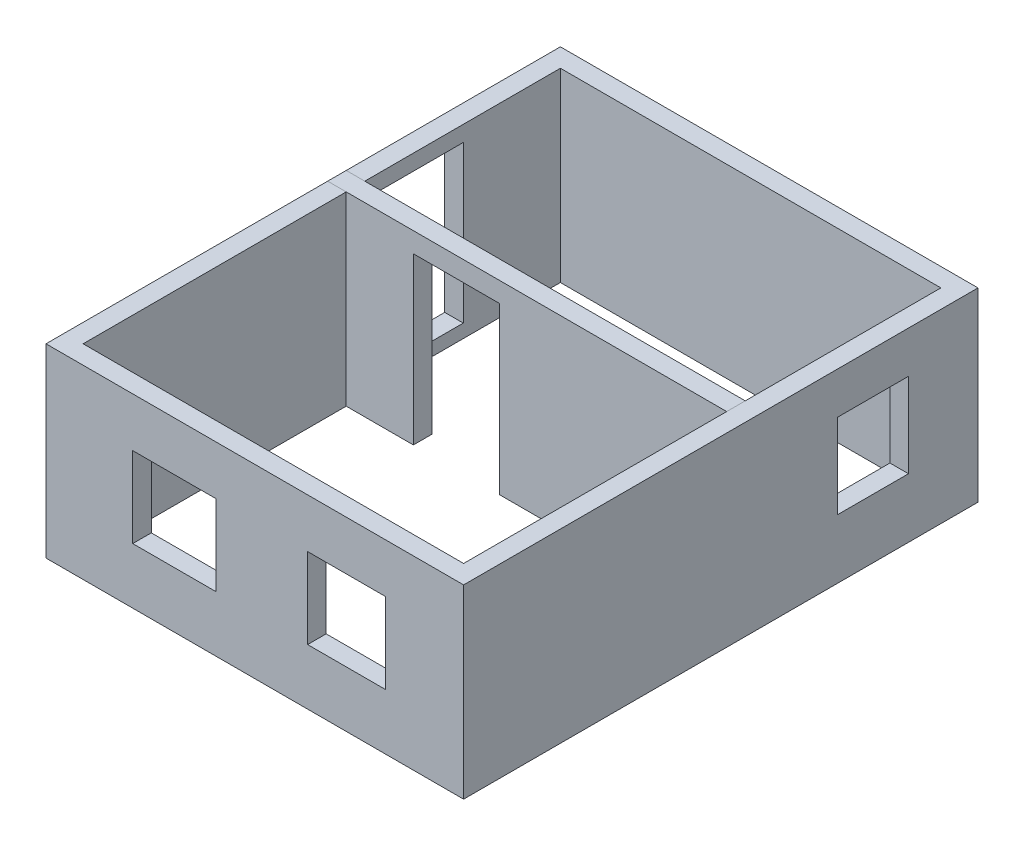
SolidWorks part; units mm, degrees
ref_plane "Спереди" through (0, 0, 0) normal (0, 0, 1) x (1, 0, 0)
ref_plane "Сверху" through (0, 0, 0) normal (0, 1, 0) x (1, 0, 0)
ref_plane "Справа" through (0, 0, 0) normal (1, 0, 0) x (0, 0, -1)
sketch "Эскиз2" plane through (0, 0, 0) normal (0, 1, 0) x (-1, 0, 0)
  line L0 (-4500, -3235.0443) -> (0, -3235.0443)
  line L1 (-4500, 0) -> (0, 0)
  line L2 (-4500, 0) -> (-4500, -5543)
  line L3 (-4500, -5543) -> (0, -5543)
  line L4 (0, 0) -> (0, -5543)
  dimension "D1" = 4500
  dimension "D2" = 5543
extrude "Вытянуть-Тонкостенный1" add sketch "Эскиз2" along normal blind 2000 thin thin type one direction reverse wall 200
sketch "Эскиз3" plane through (0, 0, 0) normal (0, 0, 1) x (1, 0, 0)
  line L1 (934.481, 1470.4647) -> (1829.3618, 1470.4647)
  line L2 (934.481, 1470.4647) -> (934.481, 602.7015)
  line L3 (934.481, 602.7015) -> (1829.3618, 602.7015)
  line L4 (1829.3618, 1470.4647) -> (1829.3618, 602.7015)
  line L5 (2819.1542, 1470.4647) -> (3659.7997, 1470.4647)
  line L6 (2819.1542, 1470.4647) -> (2819.1542, 602.7015)
  line L7 (2819.1542, 602.7015) -> (3659.7997, 602.7015)
  line L8 (3659.7997, 1470.4647) -> (3659.7997, 602.7015)
extrude "Вырез-Вытянуть1" cut sketch "Эскиз3" against normal up to surface (200 mm away) up to face at (2250, 1000, -200)
sketch "Эскиз4" plane through (0, 0, -3035.0443) normal (0, 0, 1) x (1, 0, 0)
  line L0 (0, 0) -> (4500, 0) construction
  line L1 (923.4902, 1784.6258) -> (1849.772, 1784.6258)
  line L2 (923.4902, 1784.6258) -> (923.4902, 0)
  line L3 (923.4902, 0) -> (1849.772, 0)
  line L4 (1849.772, 1784.6258) -> (1849.772, 0)
extrude "Вырез-Вытянуть2" cut sketch "Эскиз4" against normal up to surface (200 mm away) up to face at (2250, 1000, -3235.0443)
sketch "Эскиз5" plane through (4500, 0, 0) normal (1, 0, 0) x (0, 0, -1)
  line L1 (4026.9645, 1549.687) -> (4793.8824, 1549.687)
  line L2 (4026.9645, 1549.687) -> (4026.9645, 640.3415)
  line L3 (4026.9645, 640.3415) -> (4793.8824, 640.3415)
  line L4 (4793.8824, 1549.687) -> (4793.8824, 640.3415)
extrude "Вырез-Вытянуть3" cut sketch "Эскиз5" against normal up to surface (200 mm away) up to face at (4300, 1000, -2771.5)
sketch "Эскиз6" plane through (0, 0, 0) normal (-1, 0, 0) x (0, 0, 1)
  line L1 (-4296.452, 1830.6847) -> (-3365.8902, 1830.6847)
  line L2 (-4296.452, 1830.6847) -> (-4296.452, 144.955)
  line L3 (-4296.452, 144.955) -> (-3365.8902, 144.955)
  line L4 (-3365.8902, 1830.6847) -> (-3365.8902, 144.955)
extrude "Вырез-Вытянуть4" cut sketch "Эскиз6" against normal up to surface (200 mm away) up to face at (200, 1000, -2771.5)
